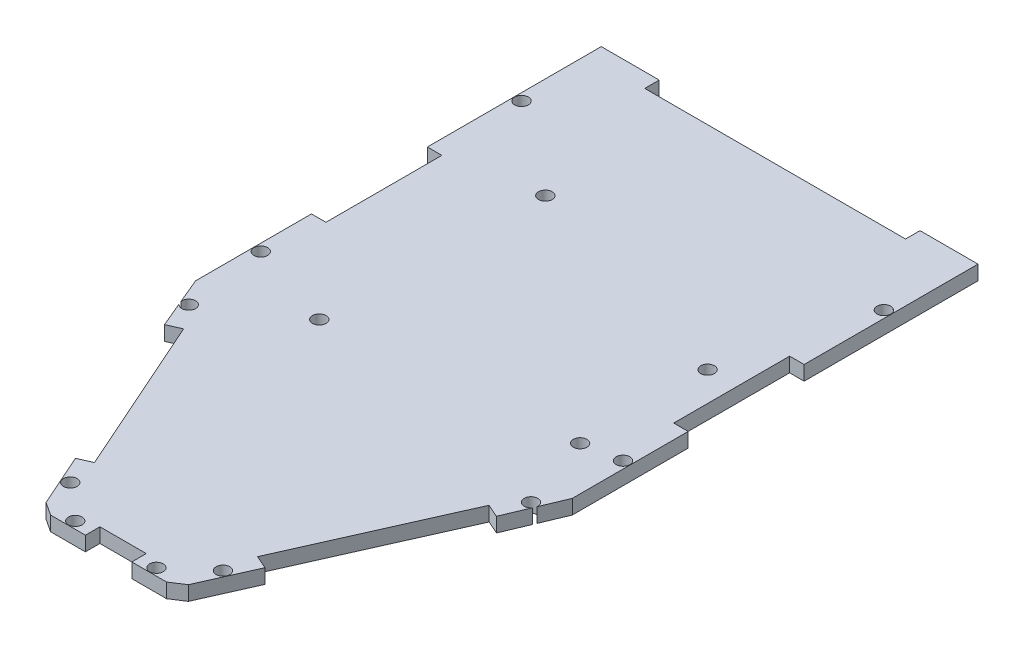
SolidWorks part; units mm, degrees
ref_plane "Front Plane" through (0, 0, 0) normal (0, 0, 1) x (1, 0, 0)
ref_plane "Top Plane" through (0, 0, 0) normal (0, 1, 0) x (1, 0, 0)
ref_plane "Right Plane" through (0, 0, 0) normal (1, 0, 0) x (0, 0, -1)
sketch "Sketch1" plane through (0, 0, 0) normal (0, 1, 0) x (1, 0, 0)
  line L0 (-41.275, 0) -> (-36.3683, -11.7139)
  line L1 (3.175, 88.9) -> (3.175, 85.725) construction
  line L2 (28.575, 85.725) -> (3.175, 85.725)
  line L3 (-41.275, 88.9) -> (-28.575, 88.9)
  line L4 (28.575, 88.9) -> (28.575, 85.725)
  line L5 (41.275, 50.8) -> (41.275, 88.9)
  line L6 (-41.275, 0) -> (-38.1, 0) construction
  line L7 (-41.275, 50.8) -> (-38.1, 50.8)
  line L8 (0, 63.5) -> (0, -63.5) construction
  line L9 (38.1, 50.8) -> (38.1, 25.4)
  line L10 (-38.1, 50.8) -> (-38.1, 25.4)
  line L11 (-41.275, 50.8) -> (-41.275, 88.9)
  line L12 (41.275, 50.8) -> (38.1, 50.8)
  line L13 (-28.575, 88.9) -> (-28.575, 85.725)
  line L14 (-28.575, 85.725) -> (-3.175, 85.725)
  line L15 (-3.175, 88.9) -> (-3.175, 85.725) construction
  line L16 (41.275, 88.9) -> (28.575, 88.9)
  line L17 (-41.275, 0) -> (41.275, 0) construction
  line L18 (-38.1, 0) -> (-38.1, 25.4) construction
  line L19 (-38.1, 25.4) -> (-41.275, 25.4)
  line L20 (-3.175, 88.9) -> (3.175, 88.9) construction
  line L21 (-41.275, 0) -> (-41.275, 25.4)
  line L22 (38.1, 25.4) -> (41.275, 25.4)
  line L23 (-38.1, 0) -> (-33.467, -10.4244) construction
  line L24 (41.275, 0) -> (41.275, 25.4)
  line L25 (33.467, -10.4244) -> (38.1, 0) construction
  line L26 (-36.3683, -11.7139) -> (-33.467, -10.4244) construction
  line L27 (41.275, 0) -> (36.3683, -11.7139)
  line L28 (36.3683, -11.7139) -> (33.467, -10.4244) construction
  line L29 (-17.858, -45.5446) -> (-12.7, -57.15) construction
  line L30 (-12.7, -57.15) -> (-15.6014, -58.4395) construction
  line L31 (-17.858, -45.5446) -> (-20.7593, -46.8341)
  line L32 (-15.6014, -58.4395) -> (-20.7593, -46.8341)
  line L33 (12.7, -57.15) -> (17.858, -45.5446) construction
  line L34 (-33.467, -10.4244) -> (-17.858, -45.5446)
  line L35 (-12.7, -57.15) -> (12.7, -57.15) construction
  line L36 (17.858, -45.5446) -> (33.467, -10.4244)
  line L37 (-3.175, 85.725) -> (3.175, 85.725)
  line L38 (41.275, 69.85) -> (-41.275, 69.85) construction
  line L39 (12.7, -57.15) -> (15.6014, -58.4395) construction
  line L40 (17.858, -45.5446) -> (20.7593, -46.8341)
  line L41 (15.6014, -58.4395) -> (20.7593, -46.8341)
  line L42 (38.1, 0) -> (38.1, 25.4) construction
  line L43 (-15.6014, -58.4395) -> (-12.7, -60.325)
  line L44 (-5.08, -57.15) -> (-12.7, -57.15) construction
  line L45 (-5.08, -57.15) -> (-5.08, -60.325)
  line L46 (-5.08, -60.325) -> (-12.7, -60.325)
  line L47 (-12.7, -57.15) -> (-12.7, -60.325) construction
  line L48 (5.08, -57.15) -> (12.7, -57.15) construction
  line L49 (5.08, -57.15) -> (5.08, -60.325)
  line L50 (5.08, -60.325) -> (12.7, -60.325)
  line L51 (12.7, -57.15) -> (12.7, -60.325) construction
  line L52 (15.6014, -58.4395) -> (12.7, -60.325)
  line L53 (-5.08, -57.15) -> (5.08, -57.15)
  line L54 (33.467, -10.4244) -> (36.3683, -11.7139)
  line L55 (-33.467, -10.4244) -> (-36.3683, -11.7139)
  point P0 (0, 0)
  point P1 (0, -57.15)
  dimension "D1" = 25.4
  dimension "D2" = 57.15
  dimension "D3" = 3.175
  dimension "D4" = 82.55
  dimension "D5" = 3.175
  dimension "D6" = 12.7
  dimension "D7" = 25.4
  dimension "D8" = 38.1
  dimension "D9" = 50.8
  dimension "D10" = 25.4
  dimension "D11" = 12.7
  dimension "D12" = 12.7
  dimension "D13" = 10.16
extrude "Boss-Extrude1" add sketch "Sketch1" along normal blind 3.175
sketch "Sketch2" plane through (0, 0, 0) normal (0, -1, 0) x (-1, 0, 0)
  line L0 (39.6875, 50.8) -> (39.6875, 88.9) construction
  line L1 (41.275, 50.8) -> (38.1, 50.8) construction
  line L2 (28.575, 88.9) -> (41.275, 88.9) construction
  line L3 (0, 85.725) -> (0, -57.15) construction
  line L6 (-5.08, -58.7375) -> (-15.1428, -58.7375) construction
  line L7 (5.08, -57.15) -> (-5.08, -57.15) construction
  line L10 (28.575, 88.9) -> (41.275, 88.9) construction
  line L11 (39.6875, 25.4) -> (39.6875, -3.7899) construction
  line L12 (38.1, 25.4) -> (41.275, 25.4) construction
  line L14 (-28.575, 85.725) -> (28.575, 85.725) construction
  line L15 (41.275, 0) -> (36.3683, -11.7139) construction
  line L18 (34.9176, -11.0691) -> (41.275, 3.235) construction
  line L23 (36.3683, -11.7139) -> (33.467, -10.4244) construction
  line L24 (41.275, 25.4) -> (41.275, 0) construction
  line L25 (19.3086, -46.1893) -> (13.0261, -60.325) construction
  line L26 (17.858, -45.5446) -> (20.7593, -46.8341) construction
  line L27 (12.7, -60.325) -> (5.08, -60.325) construction
  line L28 (5.08, -58.7375) -> (15.1428, -58.7375) construction
  line L29 (5.08, -60.325) -> (5.08, -57.15) construction
  line L30 (15.6014, -58.4395) -> (12.7, -60.325) construction
  line L31 (-19.3086, -46.1893) -> (-13.0261, -60.325) construction
  line L32 (-34.9176, -11.0691) -> (-41.275, 3.235) construction
  line L33 (-39.6875, 25.4) -> (-39.6875, -3.7899) construction
  line L34 (-39.6875, 50.8) -> (-39.6875, 88.9) construction
  circle A0 centre (39.6875, 69.85) radius 1.5
  circle A1 centre (-8.89, -58.7375) radius 1.5
  circle A2 centre (39.6875, 12.7) radius 1.5
  circle A3 centre (37.4966, -5.2664) radius 1.5
  circle A4 centre (16.7297, -51.992) radius 1.5
  circle A5 centre (8.89, -58.7375) radius 1.5
  circle A6 centre (-16.7297, -51.992) radius 1.5
  circle A7 centre (-37.4966, -5.2664) radius 1.5
  circle A8 centre (-39.6875, 12.7) radius 1.5
  circle A9 centre (-39.6875, 69.85) radius 1.5
  dimension "D1" = 3
  dimension "D4" = 6.35
  dimension "D6" = 3.81
  dimension "D2" = 3
  dimension "D3" = 12.7
  dimension "D5" = 6.35
extrude "Cut-Extrude1" cut sketch "Sketch2" against normal through all
sketch "Sketch4" plane through (0, 3.175, 0) normal (0, 1, 0) x (1, 0, 0)
  circle A0 centre (31.6815, 11.305) radius 1.5
  circle A1 centre (31.6815, 39.245) radius 1.5
  circle A2 centre (-20.3885, 6.225) radius 1.5
  circle A3 centre (-19.1185, 54.485) radius 1.5
  dimension "D1" = 3
  dimension "D2" = 3
  dimension "D3" = 3
  dimension "D4" = 3
extrude "Cut-Extrude3" cut sketch "Sketch4" against normal through all
